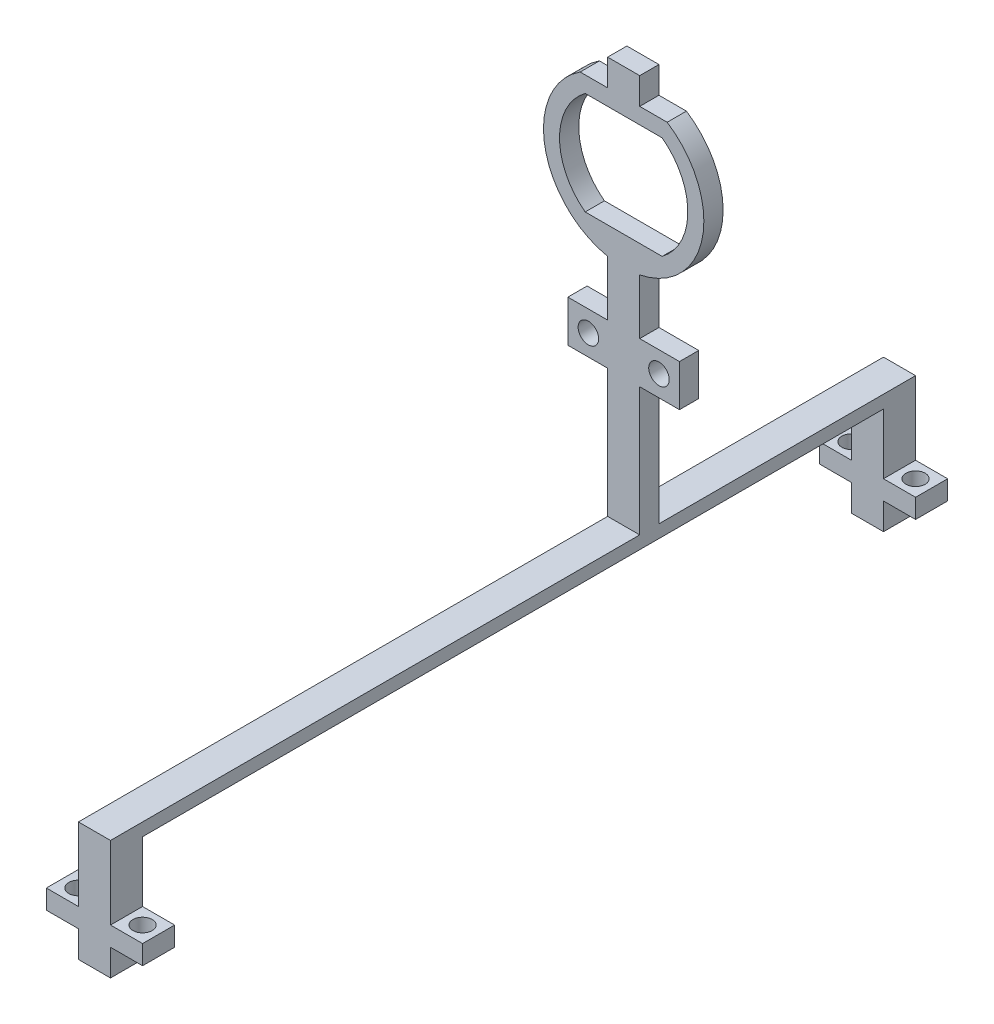
SolidWorks part; units mm, degrees
ref_plane "Front Plane" through (0, 0, 0) normal (0, 0, 1) x (1, 0, 0)
ref_plane "Top Plane" through (0, 0, 0) normal (0, 1, 0) x (1, 0, 0)
ref_plane "Right Plane" through (0, 0, 0) normal (1, 0, 0) x (0, 0, -1)
sketch "Sketch1" plane through (0, 0, 0) normal (0, 0, 1) x (1, 0, 0)
  line L5 (-18.4746, 0) -> (14.4817, 0) construction
  line L8 (0, 0) -> (0, 29.3453) construction
  line L13 (2.5, -49.3474) -> (2.5, -12.2474)
  line L18 (-2.5, -49.3474) -> (-2.5, -12.2474)
  line L21 (2.5, -49.3474) -> (-2.5, -49.3474)
  line L22 (6.7823, 10.5) -> (-6.7823, 10.5)
  line L24 (-6, -8) -> (6, -8)
  line L25 (-6, 8) -> (6, 8)
  arc A0 (-6, 8) -> (-6, -8) centre (0, 0) ccw
  arc A2 (-6.7823, 10.5) -> (-2.5, -12.2474) centre (0, 0) ccw
  arc A3 (2.5, -12.2474) -> (6.7823, 10.5) centre (0, 0) ccw
  arc A4 (6, -8) -> (6, 8) centre (0, 0) ccw
  dimension "D1" = 16
  dimension "D3" = 3.5
  dimension "D4" = 37.1
  dimension "D2" = 10
  dimension "D6" = 12.5
  dimension "D8" = 10
  dimension "D9" = 12.5
  dimension "D5" = 5
  dimension "D7" = 2.5
extrude "Boss-Extrude1" add sketch "Sketch1" along normal blind 3 contours A3 A2 A0 region at (0, -15.733, 0)
sketch "Sketch3" plane through (0, 0, 0) normal (0, 0, 1) x (1, 0, 0)
  line L0 (0, -46.1586) -> (0, 0.6217) construction
  line L1 (8.7, -20.8474) -> (-8.7, -20.8474)
  line L2 (8.7, -20.8474) -> (8.7, -27.3474)
  line L3 (8.7, -27.3474) -> (-8.7, -27.3474)
  line L4 (-8.7, -20.8474) -> (-8.7, -27.3474)
  line L5 (8.7, -20.8474) -> (-8.7, -27.3474) construction
  line L6 (8.7, -27.3474) -> (-8.7, -20.8474) construction
  line L7 (2.5, -49.3474) -> (-2.5, -49.3474) construction
  circle A0 centre (-5.5, -24.0974) radius 1.6
  circle A1 centre (5.5, -24.0974) radius 1.6
  point P0 (0, -24.0974)
  dimension "D4" = 3.2
  dimension "D5" = 3.2
  dimension "D6" = 3.25
  dimension "D1" = 11
  dimension "D2" = 6.5
  dimension "D3" = 22
extrude "Boss-Extrude4" add sketch "Sketch3" along normal blind 3
sketch "Sketch11" plane through (0, 10.5, 0) normal (0, 1, 0) x (1, 0, 0)
  line L0 (6.7823, -3) -> (-6.7823, -3) construction
  line L1 (-2.5, 0) -> (2.5, 0)
  line L2 (-2.5, 0) -> (-2.5, -3)
  line L3 (-2.5, -3) -> (2.5, -3)
  line L4 (2.5, 0) -> (2.5, -3)
  line L5 (-2.5, 0) -> (2.5, -3) construction
  line L6 (-2.5, -3) -> (2.5, 0) construction
  line L11 (6.7823, 0) -> (-6.7823, 0) construction
  point P0 (0, -1.5)
  point P10 (0, 0)
  dimension "D1" = 3
  dimension "D2" = 5
extrude "Boss-Extrude8" add sketch "Sketch11" along normal blind 4.15
sketch "Sketch6" plane through (0, 0, 0) normal (0, 0, -1) x (-1, 0, 0)
  line L0 (2.5, -49.3474) -> (2.5, -27.3474) construction
  line L1 (-2.5, -49.3474) -> (2.5, -49.3474)
  line L2 (-2.5, -49.3474) -> (-2.5, -47.3474)
  line L3 (-2.5, -47.3474) -> (2.5, -47.3474)
  line L4 (2.5, -49.3474) -> (2.5, -47.3474)
  dimension "D1" = 2
extrude "Boss-Extrude5" add sketch "Sketch6" along normal blind 40
sketch "Sketch10" plane through (0, 0, 3) normal (0, 0, 1) x (1, 0, 0)
  line L0 (-2.5, -49.3474) -> (-2.5, -27.3474) construction
  line L1 (2.5, -49.3474) -> (-2.5, -49.3474)
  line L2 (2.5, -49.3474) -> (2.5, -47.3474)
  line L3 (2.5, -47.3474) -> (-2.5, -47.3474)
  line L4 (-2.5, -49.3474) -> (-2.5, -47.3474)
  dimension "D1" = 2
extrude "Boss-Extrude7" add sketch "Sketch10" along normal blind 82.49
sketch "Sketch14" plane through (0, 0, -40) normal (0, 0, -1) x (-1, 0, 0)
  line L0 (-2.5, -61.7674) -> (-2.5, -65.9174)
  line L5 (-2.5, -49.3474) -> (2.5, -49.3474)
  line L6 (-2.5, -49.3474) -> (-2.5, -58.7674)
  line L7 (-2.5, -65.9174) -> (2.5, -65.9174)
  line L8 (2.5, -49.3474) -> (2.5, -58.7674)
  line L9 (-7.5, -61.7674) -> (-2.5, -61.7674)
  line L10 (-7.5, -61.7674) -> (-7.5, -58.7674)
  line L11 (-7.5, -58.7674) -> (-2.5, -58.7674)
  line L12 (7.5, -61.7674) -> (7.5, -58.7674)
  line L13 (2.5, -61.7674) -> (2.5, -65.9174)
  line L14 (2.5, -58.7674) -> (7.5, -58.7674)
  line L15 (2.5, -61.7674) -> (7.5, -61.7674)
  dimension "D1" = 5
  dimension "D2" = 16.57
  dimension "D3" = 15
  dimension "D4" = 3
  dimension "D5" = 4.15
extrude "Boss-Extrude9" add sketch "Sketch14" against normal blind 5
sketch "Sketch15" plane through (0, -58.7674, 0) normal (0, 1, 0) x (1, 0, 0)
  line L0 (-7.5, 40) -> (-2.5, 40) construction
  line L1 (-7.5, 35) -> (-7.5, 40) construction
  circle A0 centre (-5, 37.5) radius 1.5
  dimension "D1" = 3
  dimension "D2" = 2.5
  dimension "D3" = 2.5
extrude "Cut-Extrude1" cut sketch "Sketch15" against normal blind 5
mirror "Mirror1" about plane through (0, 0, 0) normal (1, 0, 0) of "Cut-Extrude1"
ref_plane "Plane4" through (0, 0, 22.745) normal (0, 0, -1) x (-1, 0, 0)
mirror "Mirror2" about plane through (0, 0, 22.745) normal (0, 0, -1) of "Boss-Extrude9", "Cut-Extrude1", "Mirror1"
